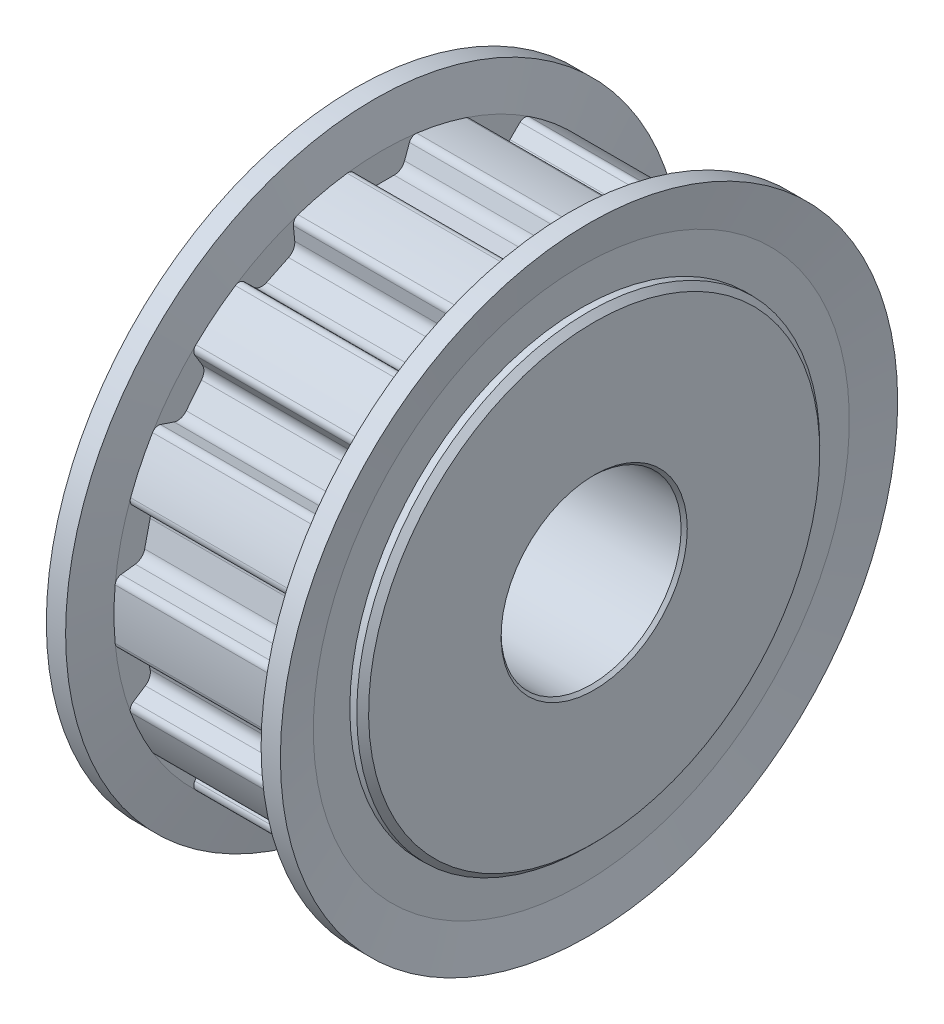
SolidWorks part; units mm, degrees
ref_plane "前视基准面" through (0, 0, 0) normal (0, 0, 1) x (1, 0, 0)
ref_plane "上视基准面" through (0, 0, 0) normal (0, 1, 0) x (1, 0, 0)
ref_plane "右视基准面" through (0, 0, 0) normal (1, 0, 0) x (0, 0, -1)
sketch "草图1" plane through (0, 0, 0) normal (1, 0, 0) x (0, 0, -1)
  line L0 (0, 0) -> (14, 0)
  line L1 (0, 0) -> (0, 21.225) construction
  line L2 (-2.1359, 20.3198) -> (-1.756, 19.2759)
  line L3 (-0.9478, 18.71) -> (0.9478, 18.71)
  line L4 (2.1359, 20.3198) -> (1.756, 19.2759)
  line L6 (-2.5, 6.5383) -> (2.5, 6.5383)
  line L7 (-2.5, 6.5383) -> (-2.5, 9.3)
  line L8 (-2.5, 9.3) -> (2.5, 9.3)
  line L9 (2.5, 6.5383) -> (2.5, 9.3)
  circle A0 centre (0, 0) radius 21.225
  arc A1 (-2.7027, 20.664) -> (20.84, 0) centre (0, 0) ccw
  arc A2 (-1.756, 19.2759) -> (-0.9478, 18.71) centre (-0.9478, 19.57) ccw
  arc A3 (-2.7027, 20.664) -> (-2.1359, 20.3198) centre (-2.6339, 20.1385) cw
  arc A4 (1.756, 19.2759) -> (0.9478, 18.71) centre (0.9478, 19.57) cw
  arc A5 (2.7027, 20.664) -> (2.1359, 20.3198) centre (2.6339, 20.1385) ccw
  circle A6 centre (0, 0) radius 7
  point P2 (1.55, 18.71)
  point P15 (0, 18.71)
  point P20 (0, 20.84)
  point P26 (0, 7)
  point P27 (-1.55, 18.71)
  dimension "D1" = 0.86
  dimension "Dr" = 42.45
  dimension "Ds" = 41.68
  dimension "D4" = 0.53
  dimension "dH7" = 14
  dimension "Z" = 14
  dimension "D2" = 3.1
  dimension "D3" = 20
  dimension "D5" = 2.13
  dimension "t" = 2.3
  dimension "b" = 5
sketch "草图2" plane through (0, 0, 0) normal (0, 0, 1) x (1, 0, 0)
  line L0 (0, 0) -> (19, 0) construction
  line L1 (0, 0) -> (0, 18)
  line L2 (0, 18) -> (2.5, 18)
  line L3 (2.5, 18) -> (2.5, 20.84)
  line L4 (2.5, 20.84) -> (16.5, 20.84)
  line L5 (16.5, 20.84) -> (16.5, 18)
  line L6 (16.5, 18) -> (19, 18)
  line L7 (19, 18) -> (19, 0)
  line L8 (0, 0) -> (0, 21.225) construction
  line L9 (1, 18) -> (1, 20.84)
  line L10 (1, 20.84) -> (0.4, 24)
  line L11 (0.4, 24) -> (1.9, 24)
  line L12 (1.9, 24) -> (2.5, 20.84)
  line L13 (2.5, 20.84) -> (2.5, 18)
  line L14 (9.5, 20.84) -> (9.5, 0) construction
  line L15 (12, 20.84) -> (12, 0)
  line L17 (19, 0.5) -> (18, 0.5)
  line L18 (0, 0.5) -> (1, 0.5)
  point P27 (3, 9)
  dimension "A" = 14
  dimension "W" = 19
  dimension "Dfi" = 36
  dimension "D2" = 2.1
  dimension "D3" = 1.5
  dimension "Dfo" = 48
  dimension "M" = 5
  dimension "S" = 3
  dimension "Dw" = 1
  dimension "F" = 1
  dimension "DsH7" = 18
  dimension "E" = 1
  dimension "Dv" = 1
sketch "草图3" plane through (0, 0, 0) normal (0, 0, 1) x (1, 0, 0)
  line L0 (0, 0) -> (0, 17.54)
  line L1 (0.46, 18) -> (2.5, 18)
  line L2 (2.5, 18) -> (2.5, 20.84)
  line L3 (2.5, 20.84) -> (16.5, 20.84)
  line L4 (16.5, 20.84) -> (16.5, 18)
  line L5 (16.5, 18) -> (18.54, 18)
  line L6 (19, 17.54) -> (19, 0)
  line L7 (19, 0) -> (0, 0)
  line L8 (0, 17.54) -> (0.46, 18)
  line L9 (18.54, 18) -> (19, 17.54)
  point P1 (0, 18)
  point P13 (19, 18)
  dimension "D1" = 0.46
  dimension "D2" = 45
  dimension "D4" = 45
revolve "旋转1" add sketch "草图3" angle 360 about L7
sketch "草图4" plane through (0, 0, 0) normal (1, 0, 0) x (0, 0, -1)
  line L0 (-0.9478, 18.71) -> (0.9478, 18.71) construction
  line L1 (2.1359, 20.3198) -> (1.756, 19.2759) construction
  line L2 (-2.1359, 20.3198) -> (-1.756, 19.2759) construction
  line L3 (-0.9478, 18.71) -> (0.9478, 18.71)
  line L4 (2.1359, 20.3198) -> (1.756, 19.2759)
  line L5 (-2.1359, 20.3198) -> (-1.756, 19.2759)
  arc A0 (0.9478, 18.71) -> (1.756, 19.2759) centre (0.9478, 19.57) ccw construction
  arc A1 (2.7027, 20.664) -> (2.1359, 20.3198) centre (2.6339, 20.1385) ccw construction
  arc A2 (-1.756, 19.2759) -> (-0.9478, 18.71) centre (-0.9478, 19.57) ccw construction
  arc A3 (-2.1359, 20.3198) -> (-2.7027, 20.664) centre (-2.6339, 20.1385) ccw construction
  arc A4 (0.9478, 18.71) -> (1.756, 19.2759) centre (0.9478, 19.57) ccw
  arc A5 (2.7027, 20.664) -> (2.1359, 20.3198) centre (2.6339, 20.1385) ccw
  arc A6 (-1.756, 19.2759) -> (-0.9478, 18.71) centre (-0.9478, 19.57) ccw
  arc A7 (-2.1359, 20.3198) -> (-2.7027, 20.664) centre (-2.6339, 20.1385) ccw
  arc A8 (-2.7027, 20.664) -> (20.84, 0) centre (0, 0) ccw construction
  arc A9 (2.7027, 20.664) -> (-2.7027, 20.664) centre (0, 0) ccw
extrude "切除-拉伸1" cut sketch "草图4" along normal up to vertex (16.5 mm away) from vertex up to point (16.5, 20.84, 0) starting at point (2.5, 20.84, 0)
pattern_circular "阵列(圆周)1" count 14 over 360 about axis through (19, 0, 0) along (1, 0, 0) of "切除-拉伸1"
sketch "草图5" plane through (0, 0, 0) normal (0, 0, 1) x (1, 0, 0)
  line L0 (1.9, 24) -> (2.5, 20.84) construction
  line L1 (0.4, 24) -> (1.9, 24) construction
  line L2 (1, 20.84) -> (0.4, 24) construction
  line L3 (1, 18) -> (1, 20.84) construction
  line L4 (2.5, 18) -> (2.5, 20.84) construction
  line L5 (1.9, 24) -> (2.5, 20.84)
  line L6 (0.4, 24) -> (1.9, 24)
  line L7 (1, 20.84) -> (0.4, 24)
  line L8 (1, 18) -> (1, 20.84)
  line L9 (2.5, 18) -> (2.5, 20.84)
  line L10 (1, 18) -> (2.5, 18)
  line L11 (0, 0) -> (19, 0) construction
  line L12 (9.5, 20.84) -> (9.5, 0) construction
  line L13 (18, 18) -> (16.5, 18)
  line L14 (18, 18) -> (18, 20.84)
  line L15 (18, 20.84) -> (18.6, 24)
  line L16 (18.6, 24) -> (17.1, 24)
  line L17 (17.1, 24) -> (16.5, 20.84)
  line L18 (16.5, 18) -> (16.5, 20.84)
revolve "旋转2" add sketch "草图5" angle 360 about L11
sketch "草图6" plane through (0, 0, 0) normal (1, 0, 0) x (0, 0, -1)
  circle A0 centre (0, 0) radius 7 construction
  circle A1 centre (0, 0) radius 7
extrude "切除-拉伸2" cut sketch "草图6" along normal through all
chamfer "倒角1" distance 0.24 angle 45 2 edges at (0, 0, -7) (19, 0, -7)
sketch "草图7" [suppressed] plane through (0, 0, 0) normal (1, 0, 0) x (0, 0, -1)
  line L0 (-1.5, 2) -> (1.5, 2) construction
  line L1 (1.5, 2) -> (1.5, 3.9) construction
  line L2 (-1.5, 3.9) -> (1.5, 3.9) construction
  line L3 (-1.5, 2) -> (-1.5, 3.9) construction
  line L4 (-1.5, 2) -> (1.5, 2)
  line L5 (1.5, 2) -> (1.5, 3.9)
  line L6 (-1.5, 3.9) -> (1.5, 3.9)
  line L7 (-1.5, 2) -> (-1.5, 3.9)
extrude "键槽孔1" [suppressed] cut sketch "草图7" along normal up to vertex
sketch "草图8" plane through (0, 0, 0) normal (0, 0, 1) x (1, 0, 0)
  line L0 (0, 0) -> (19, 0) construction
  line L1 (-1, 9) -> (3, 9)
  line L2 (-1, 9) -> (-1, 0)
  line L3 (-1, 0) -> (3, 0)
  line L4 (3, 9) -> (3, 0)
  point P4 (0, 9)
  dimension "D1" = 1
revolve "旋转3" add sketch "草图8" angle 360 about L3
revolve "切除-旋转4" cut sketch "草图8<3>" angle 360 about L3
sketch "草图8<3>" plane through (0, 0, 0) normal (0, 0, 1) x (1, 0, 0) same geometry as "草图8"
sketch "草图10" plane through (0, 0, 0) normal (0, 0, 1) x (1, 0, 0)
  line L0 (9.5, 20.84) -> (9.5, 0) construction
  line L1 (18, 0.5) -> (19, 0.5)
  line L2 (18, 0.5) -> (18, 0)
  line L3 (18, 0) -> (19, 0)
  line L4 (19, 0.5) -> (19, 0)
  line L5 (0, 0) -> (0, 18) construction
  line L6 (0, 0) -> (1, 0)
  line L7 (0, 0) -> (0, 0.5)
  line L8 (0, 0.5) -> (1, 0.5)
  line L9 (1, 0) -> (1, 0.5)
revolve "两端沉孔" [suppressed] cut sketch "草图10" angle 360 about L6
sketch "草图11" [suppressed] plane through (0, 0, 0) normal (0, 0, 1) x (1, 0, 0)
  line L0 (6.25, 11.065) -> (6.25, 0) construction
  line L1 (2.5, 11.065) -> (10, 11.065) construction
  line L2 (8.25, 11.065) -> (8.25, 0) construction
  line L3 (0, 0) -> (12.5, 0) construction
  line L4 (6.25, 11.065) -> (6.25, 0)
  line L5 (6.25, 11.065) -> (8.25, 11.065)
  line L6 (8.25, 11.065) -> (8.25, 0)
  line L7 (6.25, 0) -> (8.25, 0)
revolve "切除-旋转5" [suppressed] cut sketch "草图11" angle 360 about L4
pattern_circular "阵列(圆周)2" [suppressed] count 2 over 120 of bodies 118
